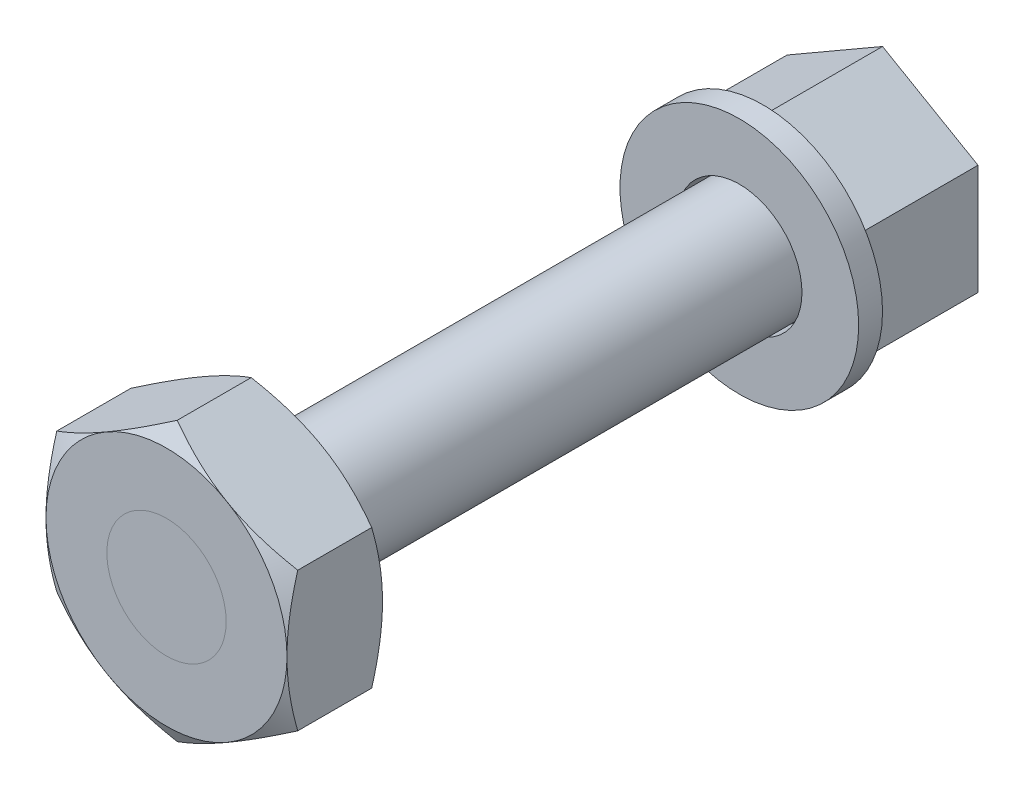
SolidWorks part; units mm, degrees
other "Vite"
other "Rosetta"
other "Dado"
ref_plane "Piano frontale" through (0, 0, 0) normal (0, 0, 1) x (1, 0, 0)
ref_plane "Piano superiore" through (0, 0, 0) normal (0, 1, 0) x (1, 0, 0)
ref_plane "Piano destro" through (0, 0, 0) normal (1, 0, 0) x (0, 0, -1)
sketch "Sketch1" plane through (0, 0, 0) normal (0, 0, 1) x (1, 0, 0)
  line L1 (-3.1632, 12.1549) -> (-11.1632, 16.7737)
  line L2 (-11.1632, 16.7737) -> (-19.1632, 12.1549)
  line L3 (-19.1632, 12.1549) -> (-19.1632, 2.9173)
  line L4 (-19.1632, 2.9173) -> (-11.1632, -1.7015)
  line L5 (-11.1632, -1.7015) -> (-3.1632, 2.9173)
  line L6 (-3.1632, 2.9173) -> (-3.1632, 12.1549)
  circle A0 centre (-11.1632, 7.5361) radius 8 construction
  circle A1 centre (-11.1632, 7.5361) radius 5
  dimension "D1" = 10
  dimension "D2" = 16
extrude "Boss-Extrude1" add sketch "Sketch1" along normal blind 10 contours A1 | L5 L6 L1 L2 L3 L4 A1 region at (-3.4076, 7.5361, 0) region at (-11.1632, 7.5361, 0)
extrude "Boss-Extrude2" add sketch "Sketch1<3>" along normal blind 50 from surface contours A1 region at (-11.1632, 7.5361, 0) starting at face at (-11.1632, 7.5361, 10)
sketch "Sketch1<3>" plane through (0, 0, 0) normal (0, 0, 1) x (1, 0, 0) same geometry as "Sketch1"
sketch "Sketch3" plane through (0, 0, 0) normal (0, 0, 1) x (1, 0, 0)
  circle A0 centre (-11.1632, 7.5361) radius 10
  circle A1 centre (-11.1632, 7.5361) radius 5 construction
  circle A2 centre (-11.1632, 7.5361) radius 5.25
  dimension "D1" = 20
  dimension "D2" = 10.5
extrude "Boss-Extrude3" add sketch "Sketch3" along normal blind 2 from surface separate body starting at face at (-6.1632, 7.5361, 10)
sketch "Sketch4" plane through (0, 0, 60) normal (0, 0, 1) x (1, 0, 0)
  line L7 (-19.1632, 12.1549) -> (-19.1632, 2.9173) construction
  line L8 (-11.1632, -4.1236) -> (-1.0656, 1.7062)
  line L9 (-1.0656, 1.7062) -> (-1.0656, 13.366)
  line L10 (-1.0656, 13.366) -> (-11.1632, 19.1958)
  line L11 (-11.1632, 19.1958) -> (-21.2608, 13.366)
  line L12 (-21.2608, 13.366) -> (-21.2608, 1.7062)
  line L13 (-21.2608, 1.7062) -> (-11.1632, -4.1236)
  circle A3 centre (-11.1632, 7.5361) radius 10.0976 construction
  circle A4 centre (-11.1632, 7.5361) radius 5 construction
  circle A5 centre (-11.1632, 7.5361) radius 5
extrude "Boss-Extrude4" add sketch "Sketch4" against normal blind 8 separate body
ref_plane "Plane1" through (0, 7.5361, 0) normal (0, -1, 0) x (-1, 0, 0)
sketch "Sketch5" plane through (0, 7.5361, 0) normal (0, -1, 0) x (-1, 0, 0)
  line L0 (28.189, -56) -> (14.3326, -64)
  line L1 (14.3326, -64) -> (14.3326, -68.5)
  line L2 (14.3326, -68.5) -> (39.3326, -68.5)
  line L3 (39.3326, -68.5) -> (39.3326, -43.5)
  line L4 (39.3326, -43.5) -> (14.3326, -43.5)
  line L5 (14.3326, -43.5) -> (14.3326, -48)
  line L6 (14.3326, -48) -> (28.189, -56)
  line L7 (14.3326, -64) -> (20.4964, -64) construction
  line L8 (14.3326, -48) -> (20.7305, -48) construction
  point P7 (21.2608, -60)
  point P10 (21.2608, -52)
  dimension "D1" = 30
  dimension "D2" = 30
  dimension "D3" = 25
  dimension "D4" = 25
ref_plane "Plane2" through (-11.1632, 0, 0) normal (1, 0, 0) x (0, 0, -1)
ref_axis "Axis1" through (-11.1632, 7.5361, 91.6) along (0, 0, 1)
revolve "Cut-Revolve1" cut sketch "Sketch5" angle 360 about axis through (-11.1632, 7.5361, 91.6) along (0, 0, 1)
